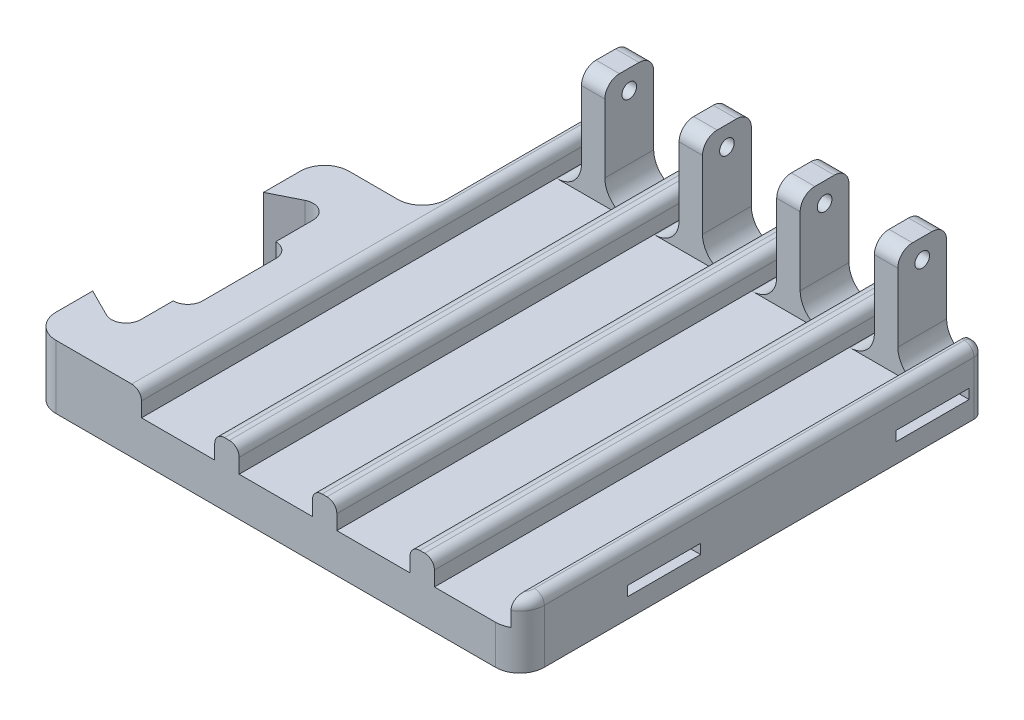
SolidWorks part; units mm, degrees
ref_plane "Alzado" through (0, 0, 0) normal (0, 0, 1) x (1, 0, 0)
ref_plane "Planta" through (0, 0, 0) normal (0, 1, 0) x (1, 0, 0)
ref_plane "Vista lateral" through (0, 0, 0) normal (1, 0, 0) x (0, 0, -1)
sketch "Croquis1" plane through (0, 0, 0) normal (1, 0, 0) x (0, 0, -1)
  line L66 (-10, 8) -> (-95, 8)
  line L67 (0, 0) -> (-95, 0)
  line L68 (0, 0) -> (0, 30)
  line L69 (0, 30) -> (-10, 30)
  line L70 (-95, 0) -> (-95, 8)
  line L71 (-10, 8) -> (-10, 30)
  circle A1 centre (-5, 26) radius 1.5
  dimension "D6" = 8
  dimension "D5" = 5
  dimension "D1" = 95
  dimension "D3" = 3
  dimension "D4" = 4
  dimension "D2" = 30
  dimension "D7" = 10
extrude "Saliente-Extruir1" add sketch "Croquis1" along normal mid plane 80
sketch "Croquis2" plane through (0, 30, 0) normal (0, 1, 0) x (1, 0, 0)
  line L5 (40, 0) -> (-40, 0) construction
  line L6 (40, 0) -> (40, -10) construction
  line L14 (-40, 0) -> (-40, -10) construction
  line L18 (-32.4, 0) -> (-27.6, 0) construction
  line L19 (-32.4, 0) -> (-32.4, -10)
  line L20 (-32.4, -10) -> (-27.6, -10) construction
  line L21 (-27.6, 0) -> (-27.6, -10)
  line L23 (-12.4, 0) -> (-7.6, 0) construction
  line L24 (-12.4, 0) -> (-12.4, -10)
  line L25 (-12.4, -10) -> (-7.6, -10) construction
  line L26 (-7.6, 0) -> (-7.6, -10)
  line L27 (7.6, 0) -> (12.4, 0) construction
  line L28 (7.6, 0) -> (7.6, -10)
  line L29 (7.6, -10) -> (12.4, -10) construction
  line L30 (12.4, 0) -> (12.4, -10)
  line L31 (27.6, 0) -> (32.4, 0) construction
  line L32 (27.6, 0) -> (27.6, -10)
  line L33 (27.6, -10) -> (32.4, -10) construction
  line L34 (32.4, 0) -> (32.4, -10)
  line L39 (-32.4, -5) -> (32.4, -5) construction
  line L40 (12.4, 0) -> (27.6, 0)
  line L41 (12.4, -10) -> (27.6, -10)
  line L42 (-7.6, 0) -> (7.6, 0)
  line L43 (-7.6, -10) -> (7.6, -10)
  line L44 (-27.6, -10) -> (-12.4, -10)
  line L45 (-27.6, 0) -> (-12.4, 0)
  line L46 (-32.4, 0) -> (-40, 0)
  line L47 (-40, 0) -> (-40, -10)
  line L48 (-40, -10) -> (-32.4, -10)
  line L49 (32.4, 0) -> (40, 0)
  line L50 (40, 0) -> (40, -10)
  line L51 (40, -10) -> (32.4, -10)
  point P23 (-30, -10)
  point P24 (-10, -10)
  point P25 (10, -10)
  point P26 (30, -10)
  point P29 (0, -5)
  dimension "D1" = 4.8
  dimension "D2" = 20
  dimension "D3" = 20
  dimension "D4" = 20
  dimension "D5" = 10
extrude "Cortar-Extruir1" cut sketch "Croquis2" against normal up to surface (22 mm away) and the other way through all up to face at (0, 8, 52.5)
fillet "Redondeo28" radius 3 8 edges at (30, 30, 10) (10, 30, 10) (-10, 30, 10) (-30, 30, 10) (-30, 30, 0) (-10, 30, 0) (30, 30, 0) (10, 30, 0)
fillet "Redondeo29" radius 5 8 edges at (-27.6, 8, 5) (-7.6, 8, 5) (12.4, 8, 5) (32.4, 8, 5) (-32.4, 8, 5) (-12.4, 8, 5) (7.6, 8, 5) (27.6, 8, 5)
sketch "Croquis29" plane through (0, 8, 0) normal (0, 1, 0) x (1, 0, 0)
  line L0 (40, -95) -> (-40, -95) construction
  line L62 (-2.5, 0) -> (2.5, 0)
  line L63 (-2.5, 0) -> (-2.5, -95)
  line L65 (-2.5, -95) -> (2.5, -95)
  line L67 (2.5, 0) -> (2.5, -95)
  line L69 (17.5, 0) -> (22.5, 0)
  line L70 (17.5, 0) -> (17.5, -95)
  line L71 (17.5, -95) -> (22.5, -95)
  line L72 (22.5, 0) -> (22.5, -95)
  line L74 (17.4, -10) -> (2.6, -10) construction
  line L75 (-17.4, 0) -> (-22.6, 0) construction
  line L76 (37.5, 0) -> (40, 0)
  line L77 (37.5, 0) -> (37.5, -95)
  line L78 (37.5, -95) -> (40, -95)
  line L79 (40, 0) -> (40, -95)
  line L80 (-40, 0) -> (-37.5, 0)
  line L81 (-40, 0) -> (-40, -95)
  line L82 (-40, -95) -> (-37.5, -95)
  line L83 (-37.5, 0) -> (-37.5, -95)
  line L84 (-22.5, 0) -> (-17.5, 0)
  line L85 (-22.5, 0) -> (-22.5, -95)
  line L86 (-22.5, -95) -> (-17.5, -95)
  line L87 (-17.5, 0) -> (-17.5, -95)
  line L88 (-27.6, -10) -> (-32.4, -10) construction
  line L89 (-2.6, -10) -> (-17.4, -10) construction
  line L90 (37.4, -10) -> (22.6, -10) construction
  line L92 (22.6, 0) -> (17.4, 0) construction
  line L93 (2.6, 0) -> (-2.6, 0) construction
  line L94 (40, 0) -> (37.4, 0) construction
  point P17 (10, -10)
  point P29 (-30, -10)
  point P32 (-10, -10)
  point P35 (30, -10)
  dimension "D1" = 15
  dimension "D2" = 7.5
  dimension "D3" = 15
  dimension "D4" = 15
  dimension "D5" = 7.5
  dimension "D7" = 15
  dimension "D8" = 7.5
  dimension "D6" = 7.5
extrude "Saliente-Extruir16" add sketch "Croquis29" along normal blind 5
sketch "Croquis19" plane through (-40, 0, 0) normal (-1, 0, 0) x (0, 0, 1)
  line L7 (95, 0) -> (0, 0) construction
  line L8 (95, 13) -> (35, 13)
  line L9 (95, 13) -> (95, 0)
  line L10 (95, 0) -> (35, 0)
  line L11 (35, 13) -> (35, 0)
  dimension "D1" = 60
extrude "Saliente-Extruir10" add sketch "Croquis19" along normal blind 20 contours L10 L11 L8 L9
fillet "Redondeo23" radius 5 4 edges at (-60, 6.5, 95) (-60, 6.5, 35) (-40, 6.5, 35) (40, 6.5, 95)
sketch "Croquis30" plane through (0, 8, 0) normal (0, 1, 0) x (1, 0, 0)
  line L0 (-60, -47.5) -> (-54.3416, -44.6708)
  line L1 (-60, -40) -> (-60, -90) construction
  line L2 (-50, -47.3541) -> (-50, -82.6459)
  line L3 (-54.3416, -85.3292) -> (-60, -82.5)
  line L4 (-60, -82.5) -> (-60, -47.5)
  arc A0 (-50, -82.6459) -> (-54.3416, -85.3292) centre (-53, -82.6459) cw
  arc A1 (-54.3416, -44.6708) -> (-50, -47.3541) centre (-53, -47.3541) cw
  point P4 (-50, -65)
  point P7 (-60, -65)
  point P9 (-60, -65)
  point P12 (-50, -87.5)
  point P15 (-50, -42.5)
  dimension "D4" = 3
  dimension "D1" = 10
  dimension "D2" = 5
  dimension "D3" = 45
extrude "Cortar-Extruir6" cut sketch "Croquis30" against normal through all both and the other way through all
sketch "Croquis4" plane through (0, 0, 0) normal (1, 0, 0) x (0, 0, -1)
  line L0 (-73, 6) -> (-58, 6)
  line L6 (-73, 6) -> (-73, 4)
  line L8 (-18, 6) -> (-3, 6)
  line L9 (-18, 6) -> (-18, 4)
  line L10 (-18, 4) -> (-3, 4)
  line L11 (-3, 6) -> (-3, 4)
  line L12 (-73, 4) -> (-58, 4)
  line L13 (-58, 6) -> (-58, 4)
  line L15 (-82.6459, 0) -> (-47.3541, 0) construction
  line L16 (-30, 0) -> (0, 0) construction
  dimension "D1" = 3
  dimension "D2" = 2
  dimension "D3" = 15
  dimension "D4" = 4
  dimension "D5" = 2
  dimension "D6" = 15
  dimension "D7" = 4
  dimension "D8" = 40
extrude "Cortar-Extruir4" cut sketch "Croquis4" against normal through all both and the other way through all
sketch "Croquis31" plane through (0, 8, 0) normal (0, 1, 0) x (1, 0, 0)
  line L0 (-50, -82.6459) -> (-50, -47.3541) construction
  line L1 (-50, -55) -> (-47, -55)
  line L2 (-50, -55) -> (-50, -76)
  line L3 (-50, -76) -> (-47, -76)
  line L4 (-47, -55) -> (-47, -76)
  line L5 (-50, -58) -> (40, -58) construction
  line L6 (-50, -73) -> (40, -73) construction
  dimension "D1" = 3
  dimension "D2" = 3
  dimension "D3" = 3
extrude "Cortar-Extruir7" cut sketch "Croquis31" against normal through all both and the other way through all
fillet "Redondeo27" radius 3 2 edges at (-47, 6.5, 55) (-47, 6.5, 76)
fillet "Redondeo34" radius 2 9 edges at (39.3301, 13, 92.5) (40, 13, 45) (-37.5, 13, 47.5) (-22.5, 13, 47.5) (-17.5, 13, 47.5) (-2.5, 13, 47.5) (2.5, 13, 47.5) (17.5, 13, 47.5) (22.5, 13, 47.5)
fillet "Redondeo35" radius 2 4 edges at (37.75, 13, 0) (39.4142, 12.4142, 0) (40, 5.5, 0) (-40, 6.5, 0)
